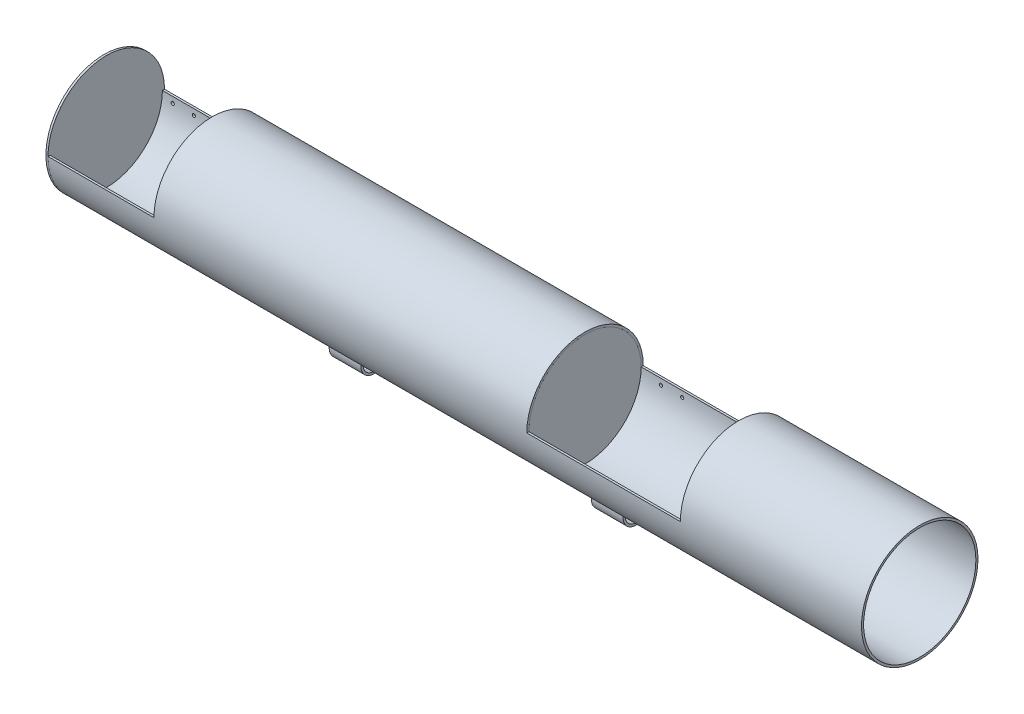
SolidWorks part; units mm, degrees
ref_plane "前视基准面" through (0, 0, 0) normal (0, 0, 1) x (1, 0, 0)
ref_plane "上视基准面" through (0, 0, 0) normal (0, 1, 0) x (1, 0, 0)
ref_plane "右视基准面" through (0, 0, 0) normal (1, 0, 0) x (0, 0, -1)
sketch "草图2" plane through (0, 0, 0) normal (1, 0, 0) x (0, 0, -1)
  circle A0 centre (0, 0) radius 55
  circle A1 centre (0, 0) radius 53
  dimension "D1" = 110
  dimension "D2" = 106
extrude "凸台-拉伸1" add sketch "草图2" along normal blind 768
ref_plane "基准面4" through (100, 0, 0) normal (1, 0, 0) x (0, 0, -1)
sketch "草图3" plane through (100, 0, 0) normal (1, 0, 0) x (0, 0, -1)
  circle A0 centre (0, 0) radius 53
extrude "凸台-拉伸2" add sketch "草图3" along normal blind 2 separate body
ref_plane "基准面5" through (400, 0, 0) normal (1, 0, 0) x (0, 0, -1)
ref_plane "基准面6" through (565, 0, 0) normal (1, 0, 0) x (0, 0, -1)
sketch "草图7" plane through (0, 0, 0) normal (1, 0, 0) x (0, 0, -1)
  circle A1 centre (0, 0) radius 55
extrude "凸台-拉伸5" add sketch "草图7" against normal blind 2 separate body
ref_plane "基准面7" through (102, 0, 0) normal (1, 0, 0) x (0, 0, -1)
ref_plane "基准面8" through (450, 0, 0) normal (1, 0, 0) x (0, 0, -1)
sketch "草图8" plane through (450, 0, 0) normal (1, 0, 0) x (0, 0, -1)
  circle A0 centre (0, 0) radius 53
extrude "凸台-拉伸6" add sketch "草图8" along normal blind 2 separate body
ref_plane "基准面9" through (507.5, 0, 0) normal (1, 0, 0) x (0, 0, -1)
ref_plane "基准面10" through (615, 0, 0) normal (1, 0, 0) x (0, 0, -1)
sketch "草图9" plane through (615, 0, 0) normal (1, 0, 0) x (0, 0, -1)
  circle A0 centre (0, 0) radius 53
sketch "草图12" plane through (0, 0, 0) normal (0, 0, 1) x (1, 0, 0)
  line L0 (615, 0) -> (565, 0)
  line L1 (615, -60.5) -> (615, 60.5) construction
  line L2 (768, 0) -> (0, 0) construction
  line L3 (565, -60.5) -> (565, 60.5) construction
sketch "草图14" plane through (0, 0, 0) normal (0, 1, 0) x (1, 0, 0)
  line L1 (452, 55) -> (597, 55)
  line L3 (452, 0) -> (597, 0)
  line L4 (597, 55) -> (597, 0)
  line L5 (768, 0) -> (0, 0) construction
  line L9 (452, 55) -> (452, 0)
  dimension "D3" = 145
ref_plane "基准面11" through (617, 0, 0) normal (1, 0, 0) x (0, 0, -1)
sketch "草图15" plane through (617, 0, 0) normal (1, 0, 0) x (0, 0, -1)
  circle A0 centre (0, 0) radius 53
revolve "切除-旋转1" cut sketch "草图14" angle 180 about L3
sketch "草图16" plane through (0, 0, 0) normal (0, 1, 0) x (1, 0, 0)
  line L0 (100, -60.5) -> (100, 60.5) construction
  line L1 (0, 0) -> (100, 0)
  line L2 (0, 0) -> (0, 55)
  line L3 (0, 55) -> (100, 55)
  line L4 (100, 0) -> (100, 55)
  line L5 (452, 55) -> (0, 55) construction
  dimension "D1" = 100
  dimension "D2" = 55
revolve "切除-旋转2" cut sketch "草图16" angle 180 about L1
ref_plane "基准面12" through (435, 0, 0) normal (1, 0, 0) x (0, 0, -1)
sketch "草图17" plane through (435, 0, 0) normal (1, 0, 0) x (0, 0, -1)
  line L0 (0, 77.9653) -> (0, -80.6413) construction
  circle A0 centre (0, -67) radius 12
  circle A1 centre (0, -67) radius 10
  circle A2 centre (0, 0) radius 55 construction
  dimension "D1" = 24
  dimension "D2" = 20
ref_plane "基准面13" through (200, 0, 0) normal (1, 0, 0) x (0, 0, -1)
ref_plane "基准面14" through (0, 0, -50) normal (0, 0, 1) x (1, 0, 0)
sketch "草图19" plane through (0, 0, -50) normal (0, 0, 1) x (1, 0, 0)
  line L0 (597, 0) -> (452, 0) construction
  line L1 (597, 55) -> (597, 0) construction
  line L2 (452, 0) -> (452, 53) construction
  circle A0 centre (574, -5.4) radius 1.5
  circle A1 centre (554, -5.4) radius 1.5
  circle A2 centre (495, -5.4) radius 1.5
  circle A3 centre (475, -5.4) radius 1.5
  dimension "D1" = 3
  dimension "D2" = 3
  dimension "D6" = 3
  dimension "D7" = 3
  dimension "D3" = 20
  dimension "D4" = 5.4
  dimension "D5" = 23
  dimension "D8" = 20
  dimension "D9" = 5.4
  dimension "D10" = 23
  dimension "D11" = 5.4
sketch "草图22" plane through (0, 0, -50) normal (0, 0, 1) x (1, 0, 0)
  line L0 (0, 0) -> (0, -55) construction
  line L1 (100, 55) -> (100, 0) construction
  line L2 (100, 0) -> (0, 0) construction
  circle A0 centre (10, -5.4) radius 1.5
  circle A1 centre (30, -5.4) radius 1.5
  circle A2 centre (70, -5.4) radius 1.5
  circle A3 centre (90, -5.4) radius 1.5
  dimension "D1" = 3
  dimension "D2" = 3
  dimension "D7" = 3
  dimension "D8" = 3
  dimension "D3" = 10
  dimension "D4" = 20
  dimension "D5" = 20
  dimension "D6" = 10
  dimension "D9" = 5.4
extrude "切除-拉伸4" cut sketch "草图22" against normal blind 30
ref_plane "基准面16" through (597, 0, 0) normal (1, 0, 0) x (0, 0, -1)
sketch "草图23" plane through (597, 0, 0) normal (1, 0, 0) x (0, 0, -1)
  circle A0 centre (0, 0) radius 53
extrude "凸台-拉伸13" add sketch "草图23" along normal blind 2 separate body
sketch "草图24" plane through (0, 0, -50) normal (0, 0, 1) x (1, 0, 0)
  line L0 (597, 0) -> (452, 0) construction
  line L1 (452, 0) -> (452, 55) construction
  line L2 (597, 55) -> (597, 0) construction
  circle A0 centre (471, -5.4) radius 1.5
  circle A1 centre (491, -5.4) radius 1.5
  circle A2 centre (558, -5.4) radius 1.5
  circle A3 centre (578, -5.4) radius 1.5
  dimension "D3" = 3
  dimension "D4" = 3
  dimension "D6" = 3
  dimension "D7" = 3
  dimension "D1" = 20
  dimension "D2" = 5.4
  dimension "D5" = 20
  dimension "D8" = 5.4
  dimension "D9" = 19
  dimension "D10" = 19
extrude "切除-拉伸5" cut sketch "草图24" against normal blind 30
ref_plane "基准面17" through (222.4934, 0, 0) normal (1, 0, 0) x (0, 0, -1)
sketch "草图25" plane through (222.4934, 0, 0) normal (1, 0, 0) x (0, 0, -1)
  circle A0 centre (0, -67) radius 12
  circle A1 centre (0, -67) radius 10
  circle A2 centre (0, 0) radius 55 construction
  dimension "D1" = 24
  dimension "D2" = 20
extrude "凸台-拉伸14" add sketch "草图25" along normal blind 30 separate body
ref_plane "基准面18" through (0, 0, 0) normal (1, 0, 0) x (0, 0, -1)
ref_plane "基准面19" through (470, 0, 0) normal (1, 0, 0) x (0, 0, -1)
sketch "草图26" plane through (470, 0, 0) normal (1, 0, 0) x (0, 0, -1)
  circle A0 centre (0, -67) radius 12
  circle A1 centre (0, -67) radius 10
extrude "凸台-拉伸15" add sketch "草图26" along normal blind 30 separate body
